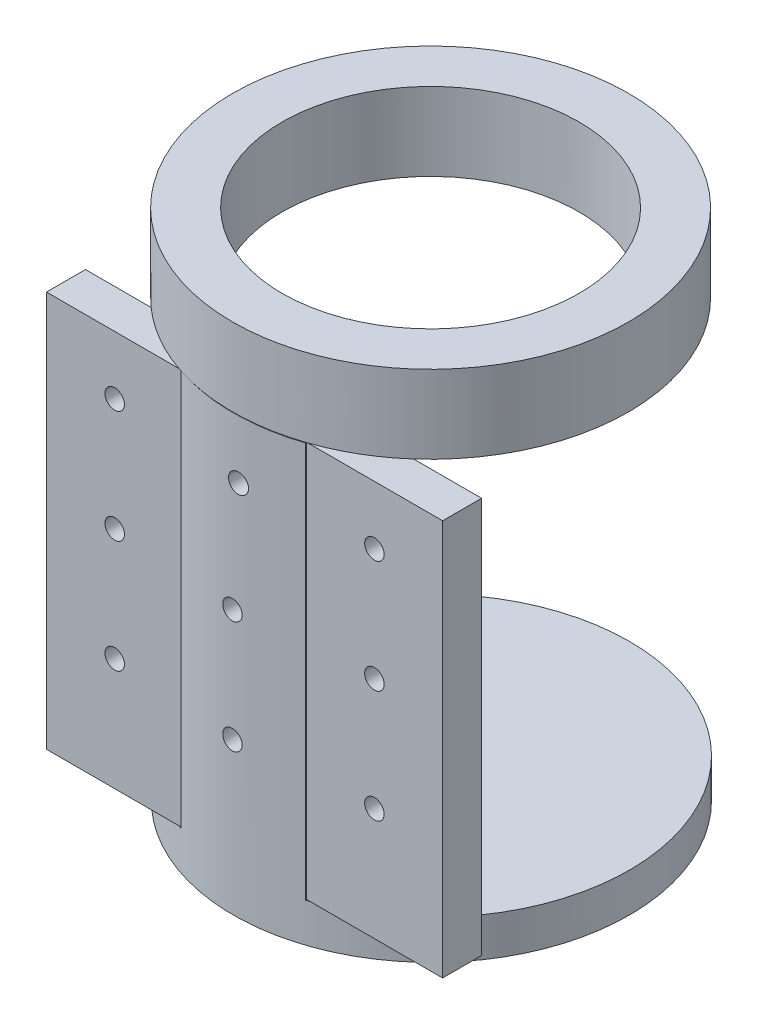
SolidWorks part; units mm, degrees
ref_plane "Front Plane" through (0, 0, 0) normal (0, 0, 1) x (1, 0, 0)
ref_plane "Top Plane" through (0, 0, 0) normal (0, 1, 0) x (1, 0, 0)
ref_plane "Right Plane" through (0, 0, 0) normal (1, 0, 0) x (0, 0, -1)
sketch "Sketch1" plane through (0, 0, 0) normal (0, 1, 0) x (1, 0, 0)
  circle A0 centre (0, 0) radius 50.8
  circle A1 centre (0, 0) radius 38.1
  dimension "D1" = 101.6
  dimension "D2" = 76.2
extrude "Boss-Extrude1" add sketch "Sketch1" along normal blind 20
sketch "Sketch2" plane through (0, 0, 0) normal (0, -1, 0) x (1, 0, 0)
  line L1 (-15.6617, 48.3255) -> (16.2462, 48.3255)
  line L2 (-15.6617, 48.3255) -> (-15.6617, 38.0246)
  line L3 (-15.6617, 38.0246) -> (16.2462, 38.0246)
  line L4 (16.2462, 48.3255) -> (16.2462, 38.0246)
  circle A0 centre (0, 0) radius 50.8 construction
extrude "Boss-Extrude2" add sketch "Sketch2" along normal blind 101.6
sketch "Sketch3" plane through (0, -101.6, 0) normal (0, -1, 0) x (1, 0, 0)
  circle A0 centre (0.2923, 0.0779) radius 50.8169
  line M5 (16.2462, 48.3255) -> (-15.6617, 48.3255)
extrude "Boss-Extrude3" add sketch "Sketch3" against normal blind 101.6 contours A0 M5 region at (0.2923, -101.6, 49.3555)
sketch "Sketch4" plane through (0, -101.6, 0) normal (0, -1, 0) x (1, 0, 0)
  circle A0 centre (0.2923, 0.0779) radius 50.8169
extrude "Boss-Extrude4" add sketch "Sketch4" along normal blind 10
ref_plane "Plane1" through (0, 0, 50.0246) normal (0, 0, -1) x (-1, 0, 0)
sketch "Sketch6" plane through (0, 0, 38.0246) normal (0, 0, -1) x (-1, 0, 0)
  line L1 (15.6617, 0) -> (50.5246, 0)
  line L2 (15.6617, 0) -> (15.6617, -101.6)
  line L3 (15.6617, -101.6) -> (50.5246, -101.6)
  line L4 (50.5246, 0) -> (50.5246, -101.6)
extrude "Boss-Extrude5" add sketch "Sketch6" against normal blind 10
sketch "Sketch7" plane through (0, 0, 38.0246) normal (0, 0, -1) x (-1, 0, 0)
  line L1 (-16.2462, 0) -> (-51.1092, 0)
  line L2 (-16.2462, 0) -> (-16.2462, -101.6)
  line L3 (-16.2462, -101.6) -> (-51.1092, -101.6)
  line L4 (-51.1092, 0) -> (-51.1092, -101.6)
extrude "Boss-Extrude6" add sketch "Sketch7" against normal blind 10
sketch "Sketch8" plane through (0, 0, 48.0246) normal (0, 0, 1) x (1, 0, 0)
  line L2 (51.1092, -101.6) -> (17.1288, -101.6) construction
  line L3 (51.1092, 0) -> (51.1092, -101.6) construction
  circle A0 centre (33.6092, -15) radius 2.5
  circle A1 centre (33.6092, -43.8667) radius 2.5
  circle A2 centre (33.6092, -72.7333) radius 2.5
  dimension "D1" = 5
  dimension "D2" = 5
  dimension "D3" = 5
  dimension "D4" = 28.8667
  dimension "D5" = 57.7333
  dimension "D6" = 86.6
  dimension "D7" = 17.5
  dimension "D8" = 17.5
  dimension "D9" = 17.5
extrude "Cut-Extrude1" cut sketch "Sketch8" against normal through all both and the other way through all
sketch "Sketch10" plane through (0, 0, 38.0246) normal (0, 0, -1) x (-1, 0, 0)
  circle A0 centre (-33.6092, -15) radius 5
  circle A1 centre (-33.6092, -43.8667) radius 5
  circle A2 centre (-33.6092, -72.7333) radius 5
  point P9 (-33.6092, -15)
  point P11 (-33.6092, -43.8667)
  point P13 (-33.6092, -72.7333)
  dimension "D1" = 10
  dimension "D2" = 10
  dimension "D3" = 10
extrude "Cut-Extrude2" cut sketch "Sketch10" against normal blind 5.15
sketch "Sketch11" plane through (0, 0, 48.0246) normal (0, 0, 1) x (1, 0, 0)
  line L0 (-50.5246, -101.6) -> (-50.5246, 0) construction
  line L1 (51.1092, -101.6) -> (-50.5246, -101.6) construction
  line L4 (-16.5443, -101.6) -> (-50.5246, -101.6) construction
  circle A0 centre (-33.0246, -15) radius 2.5
  circle A1 centre (-33.0246, -43.8667) radius 2.5
  circle A2 centre (-33.0246, -72.7333) radius 2.5
  dimension "D1" = 5
  dimension "D2" = 5
  dimension "D3" = 5
  dimension "D4" = 17.5
  dimension "D5" = 17.5
  dimension "D6" = 17.5
  dimension "D7" = 86.6
  dimension "D8" = 57.7333
  dimension "D9" = 28.8667
extrude "Cut-Extrude3" cut sketch "Sketch11" against normal through all both and the other way through all
sketch "Sketch12" plane through (0, 0, 38.0246) normal (0, 0, -1) x (-1, 0, 0)
  circle A0 centre (33.0246, -15) radius 5
  circle A1 centre (33.0246, -43.8667) radius 5
  circle A2 centre (33.0246, -72.7333) radius 5
  point P2 (33.0246, -15)
  point P5 (33.0246, -43.8667)
  point P8 (33.0246, -72.7333)
  point P9 (-3.5198, -36.6662)
  point P11 (-3.5198, -65.5329)
  point P13 (-3.5198, -94.3996)
  dimension "D1" = 10
  dimension "D2" = 10
  dimension "D3" = 10
extrude "Cut-Extrude4" cut sketch "Sketch12" against normal blind 5.15
sketch "Sketch13" plane through (0, 0, 38.0246) normal (0, 0, -1) x (-1, 0, 0)
  line L0 (33.5072, -101.6) -> (-34.0917, -101.6) construction
  circle A0 centre (-1.5496, -15) radius 2.5
  circle A1 centre (0, -43.8667) radius 2.5
  circle A2 centre (0, -72.7333) radius 2.5
  dimension "D1" = 5
  dimension "D2" = 5
  dimension "D3" = 5
  dimension "D4" = 28.8667
  dimension "D5" = 57.7333
  dimension "D6" = 86.6
extrude "Cut-Extrude5" cut sketch "Sketch13" against normal through all both and the other way through all
sketch "Sketch14" plane through (0, 0, 38.0246) normal (0, 0, -1) x (-1, 0, 0)
  circle A0 centre (-1.5496, -15) radius 5
  circle A1 centre (0, -43.8667) radius 5
  circle A2 centre (0, -72.7333) radius 5
  dimension "D1" = 10
  dimension "D2" = 10
  dimension "D3" = 10
extrude "Cut-Extrude6" cut sketch "Sketch14" against normal blind 5.15
